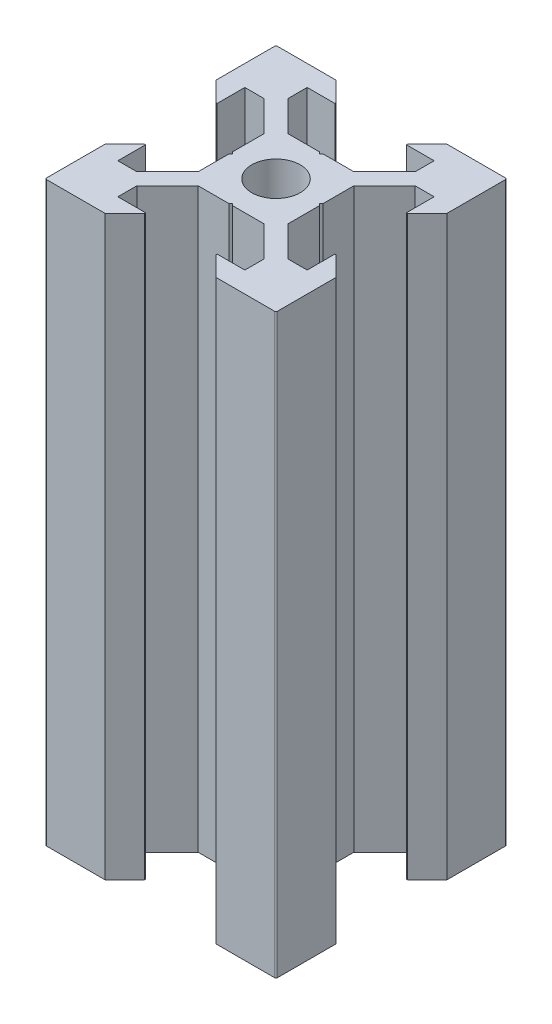
SolidWorks part; units mm, degrees
material "6063-T5"
ref_plane "Front Plane" through (0, 0, 0) normal (0, 0, 1) x (1, 0, 0)
ref_plane "Top Plane" through (0, 0, 0) normal (0, 1, 0) x (1, 0, 0)
ref_plane "Right Plane" through (0, 0, 0) normal (1, 0, 0) x (0, 0, -1)
sketch "Sketch3" plane through (0, 0, 0) normal (0, 1, 0) x (1, 0, 0)
  line L1 (-10, -10) -> (10, -10)
  line L2 (-10, -10) -> (-10, 10)
  line L3 (-10, 10) -> (10, 10)
  line L4 (10, -10) -> (10, 10)
  line L5 (-10, -10) -> (10, 10) construction
  line L6 (-10, 10) -> (10, -10) construction
  circle A0 centre (0, 0) radius 2.1
  point P0 (0, 0)
  dimension "D3" = 4.2
  dimension "D1" = 20
  dimension "D2" = 20
extrude "Boss-Extrude1" add sketch "Sketch3" along normal blind 50
sketch "Sketch4" plane through (0, 0, 0) normal (0, 1, 0) x (1, 0, 0)
  line L0 (-3.1, 10) -> (-3.1, 8.2)
  line L1 (-3.1, 8.2) -> (-5.5, 8.2)
  line L2 (-5.5, 8.2) -> (-5.5, 6.5607)
  line L3 (-5.5, 6.5607) -> (-2.8393, 3.9)
  line L4 (-2.8393, 3.9) -> (-0.15, 3.9)
  line L5 (2.8393, 3.9) -> (5.5, 6.5607)
  line L6 (5.5, 6.5607) -> (5.5, 8.2)
  line L7 (5.5, 8.2) -> (3.1, 8.2)
  line L8 (3.1, 8.2) -> (3.1, 10)
  line L9 (3.1, 10) -> (-3.1, 10)
  line L10 (0, -2.1858) -> (0, 14.6098) construction
  line L11 (-13.1925, 0) -> (14.8469, 0) construction
  line L12 (0, 0) -> (12.9337, 12.9337) construction
  line L13 (-0.15, 3.9) -> (0, 3.75)
  line L14 (0, 3.75) -> (0.15, 3.9)
  line L15 (0.15, 3.9) -> (2.8393, 3.9)
  line L16 (10, 10) -> (-10, 10) construction
  dimension "D1" = 6.2
  dimension "D2" = 6.1
  dimension "D3" = 1.8
  dimension "D4" = 11
  dimension "D5" = 10
  dimension "D6" = 45
  dimension "D7" = 0.75
  dimension "D9" = 0.3
extrude "Cut-Extrude1" cut sketch "Sketch4" along normal through all both and the other way through all
ref_axis "Axis1" through (0, 50, 0) along (0, -1, 0)
pattern_circular "CirPattern1" count 4 over 360 about axis through (0, 50, 0) along (0, -1, 0) of "Cut-Extrude1"
chamfer "Chamfer2" distance 1.7 angle 45 8 edges at (3.1, 25, -10) (-3.1, 25, -10) (-10, 25, -3.1) (10, 25, -3.1) (10, 25, 3.1) (3.1, 25, 10) (-3.1, 25, 10) (-10, 25, 3.1)
fillet "Fillet1" radius 0.14 4 edges at (-10, 25, 10) (-10, 25, -10) (10, 25, -10) (10, 25, 10)
